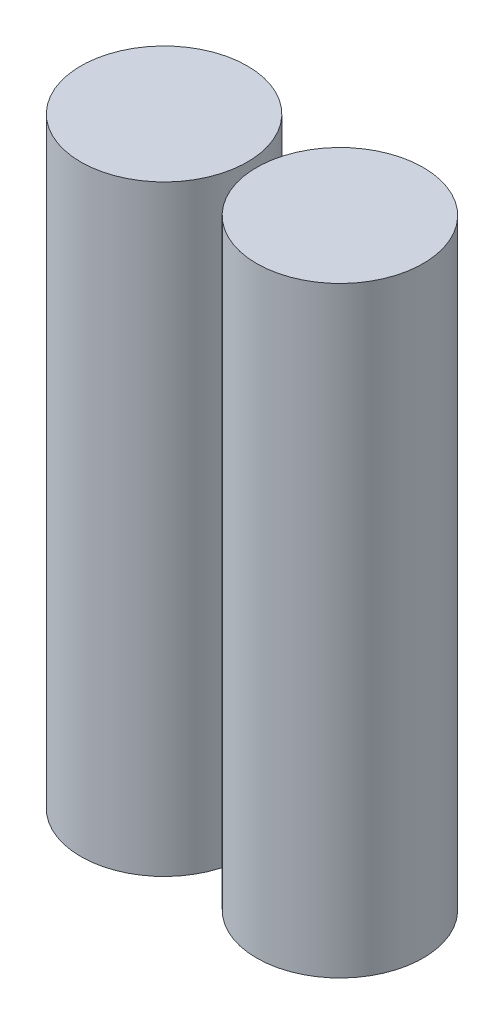
SolidWorks part; units mm, degrees
ref_plane "Front Plane" through (0, 0, 0) normal (0, 0, 1) x (1, 0, 0)
ref_plane "Top Plane" through (0, 0, 0) normal (0, 1, 0) x (1, 0, 0)
ref_plane "Right Plane" through (0, 0, 0) normal (1, 0, 0) x (0, 0, -1)
sketch "Sketch1" plane through (0, 0, 0) normal (0, 1, 0) x (1, 0, 0)
  line L0 (9, 0) -> (10, 0)
  circle A0 centre (0, 0) radius 9
  circle A1 centre (19, 0) radius 9
  dimension "D1" = 18
  dimension "D2" = 18
  dimension "D3" = 1
extrude "Boss-Extrude1" add sketch "Sketch1" along normal blind 65 contours A0 | A1 region at (19, 0, 0) region at (0, 0, 0)
